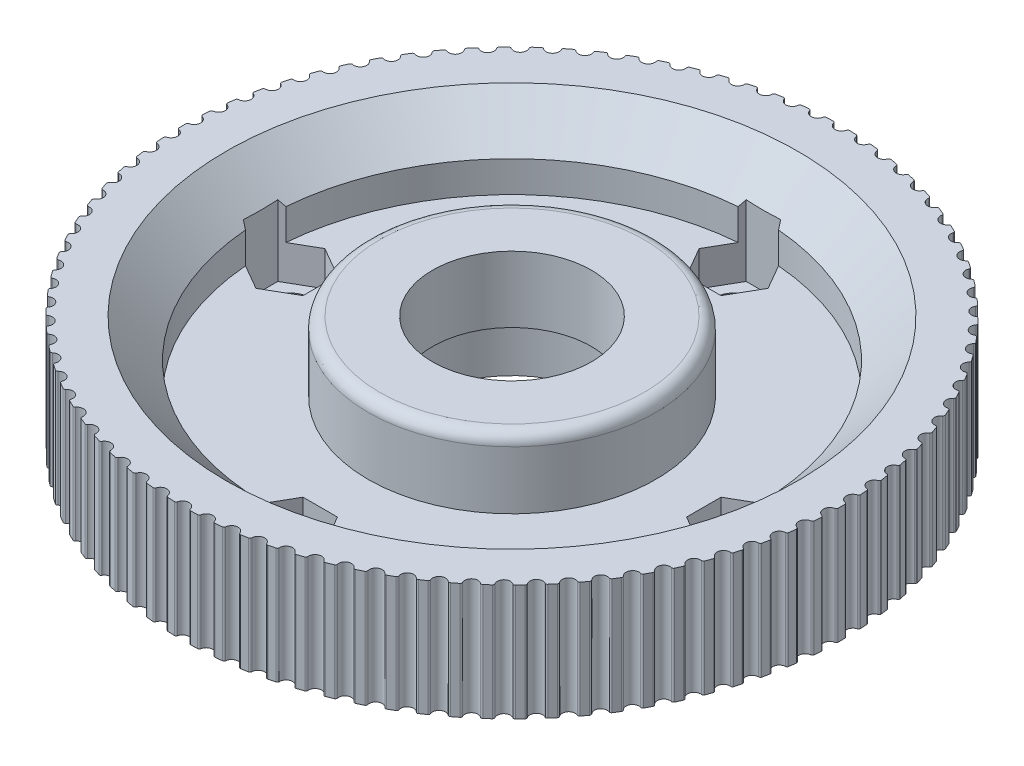
SolidWorks part; units mm, degrees
ref_plane "Front Plane" through (0, 0, 0) normal (0, 0, 1) x (1, 0, 0)
ref_plane "Top Plane" through (0, 0, 0) normal (0, 1, 0) x (1, 0, 0)
ref_plane "Right Plane" through (0, 0, 0) normal (1, 0, 0) x (0, 0, -1)
sketch "Sketch1" plane through (0, 0, 0) normal (0, 1, 0) x (1, 0, 0)
  line L0 (0, 0) -> (0, 29.7426) construction
  circle A0 centre (0, 0) radius 6.85
  circle A1 centre (0, 0) radius 7.85
  circle A2 centre (0, 19.1) radius 1.65
  circle A3 centre (19.1, 0) radius 1.65
  circle A4 centre (0, -19.1) radius 1.65
  circle A5 centre (-19.1, 0) radius 1.65
  arc A6 (-0.6958, 28.3915) -> (0.6958, 28.3915) centre (0, 0) ccw
  arc A7 (-0.5459, 28.275) -> (0.5459, 28.275) centre (0, 28.4) ccw
  arc A9 (0.6958, 28.3915) -> (0.5459, 28.275) centre (0.6921, 28.2415) ccw
  arc A11 (-0.6958, 28.3915) -> (-0.5459, 28.275) centre (-0.6921, 28.2415) cw
  point P16 (0, 0)
  point P22 (-0.2853, 28.8261)
  dimension "D1" = 19.1
  dimension "D3" = 56.8
  dimension "D4" = 3.3
  dimension "D5" = 1.12
  dimension "D6" = 13.7
  dimension "D7" = 15.7
  dimension "D2" = 4
extrude "Boss-Extrude1" add sketch "Sketch1" along normal blind 10 contours A1 A2 A7 A11 A6 A9 A5 A4 A3 | A0 A1 region at (-7.628, 0, 0) region at (-1.0929, 0, -27.7257)
ref_axis "Axis1" through (0, 10, 0) along (0, -1, 0)
pattern_circular "CirPattern1" count 90 over 360 about axis through (0, 10, 0) along (0, -1, 0) of face at (-0.6104, 5, -28.3466) of face at (0, 5, -28.0575) of face at (0.6104, 5, -28.3466)
extrude "Cut-Extrude1" cut sketch "Sketch1<3>" along normal blind 4.3 contours A1
sketch "Sketch1<3>" plane through (0, 0, 0) normal (0, 1, 0) x (1, 0, 0) same geometry as "Sketch1"
sketch "Sketch2" plane through (0, 10, 0) normal (0, 1, 0) x (1, 0, 0)
  line L0 (19.1, 2.97) -> (16.5279, 1.485)
  line L1 (-2.97, 19.1) -> (-1.485, 16.5279)
  line L2 (-1.485, 16.5279) -> (1.485, 16.5279)
  line L3 (1.485, 16.5279) -> (2.97, 19.1)
  line L4 (2.97, 19.1) -> (1.485, 21.6721)
  line L5 (1.485, 21.6721) -> (-1.485, 21.6721)
  line L6 (-1.485, 21.6721) -> (-2.97, 19.1)
  line L7 (21.6721, 1.485) -> (19.1, 2.97)
  line L8 (21.6721, -1.485) -> (21.6721, 1.485)
  line L9 (19.1, -2.97) -> (21.6721, -1.485)
  line L10 (16.5279, -1.485) -> (19.1, -2.97)
  line L11 (16.5279, 1.485) -> (16.5279, -1.485)
  line L12 (2.97, -19.1) -> (1.485, -16.5279)
  line L13 (1.485, -21.6721) -> (2.97, -19.1)
  line L14 (-1.485, -21.6721) -> (1.485, -21.6721)
  line L15 (-2.97, -19.1) -> (-1.485, -21.6721)
  line L16 (-1.485, -16.5279) -> (-2.97, -19.1)
  line L17 (1.485, -16.5279) -> (-1.485, -16.5279)
  line L18 (-19.1, -2.97) -> (-16.5279, -1.485)
  line L19 (-21.6721, -1.485) -> (-19.1, -2.97)
  line L20 (-21.6721, 1.485) -> (-21.6721, -1.485)
  line L21 (-19.1, 2.97) -> (-21.6721, 1.485)
  line L22 (-16.5279, 1.485) -> (-19.1, 2.97)
  line L23 (-16.5279, -1.485) -> (-16.5279, 1.485)
  circle A0 centre (0, 19.1) radius 2.5721 construction
  circle A1 centre (0, 0) radius 23.65
  circle A2 centre (0, 0) radius 21.3
  circle A3 centre (0, 0) radius 12.4
  point P30 (0, 0)
  dimension "D3" = 47.3
  dimension "D4" = 42.6
  dimension "D1" = 2.97
  dimension "D2" = 4
extrude "Cut-Extrude2" cut sketch "Sketch2" against normal blind 9 contours L15 A2 L13 L12 L17 L16 | L21 A2 L19 L18 L23 L22 | L9 A2 L7 L0 L11 L10 | L4 A2 L6 L1 L2 L3 region at (18.9616, 10, 0) region at (0, 10, -18.9616) region at (0, 10, 18.9616) region at (-18.9616, 10, 0)
extrude "Cut-Extrude3" cut sketch "Sketch2<3>" against normal blind 6 contours L13 A2 L9 L10 L11 L0 L7 L4 L3 L2 L1 L6 L21 L22 L23 L18 L19 L15 L16 L17 L12 A3 region at (17.5137, 10, -2.7475)
sketch "Sketch2<3>" plane through (0, 10, 0) normal (0, 1, 0) x (1, 0, 0) same geometry as "Sketch2"
chamfer "Chamfer1" distance 3.32 angle 45 1 edges at (0, 10, 21.3)
fillet "Fillet1" radius 1 1 edges at (0, 10, 12.4)
extrude "Cut-Extrude4" cut sketch "Sketch2<4>" against normal blind 9 contours L14 L13 L12 L17 L16 L15 | L8 L7 L0 L11 L10 L9 | L4 L5 L6 L1 L2 L3 | L21 L20 L19 L18 L23 L22
sketch "Sketch2<4>" plane through (0, 10, 0) normal (0, 1, 0) x (1, 0, 0) same geometry as "Sketch2"
